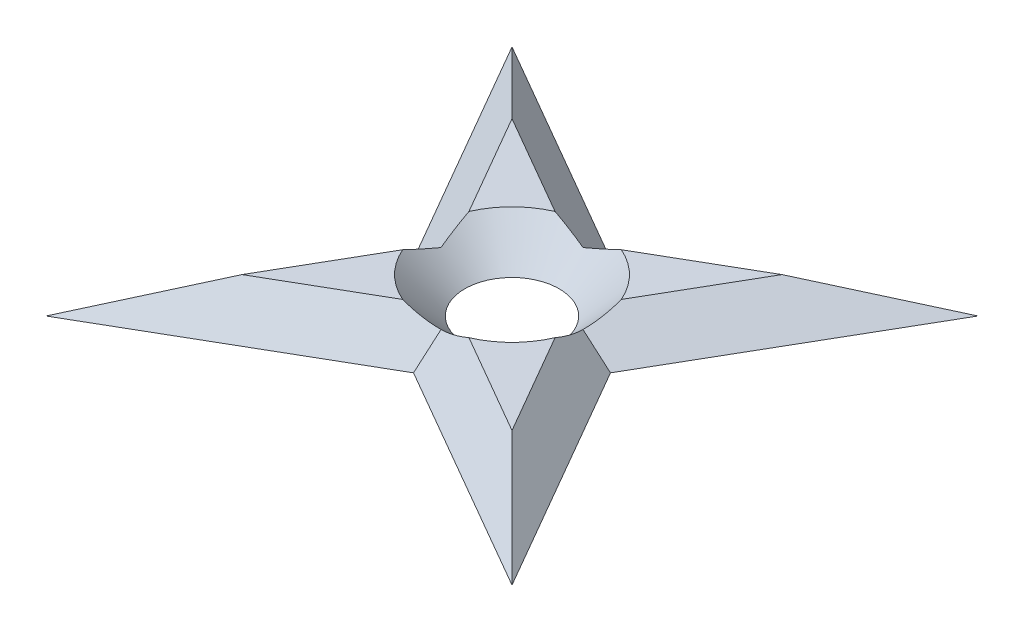
SolidWorks part; units mm, degrees
ref_plane "Front Plane" through (0, 0, 0) normal (0, 0, 1) x (1, 0, 0)
ref_plane "Top Plane" through (0, 0, 0) normal (0, 1, 0) x (1, 0, 0)
ref_plane "Right Plane" through (0, 0, 0) normal (1, 0, 0) x (0, 0, -1)
sketch "Sketch1" plane through (0, 0, 0) normal (0, 1, 0) x (1, 0, 0)
  line L0 (0, 0) -> (0, 234.4789) construction
  line L1 (0, 0) -> (250.2537, 0) construction
  line L2 (0, 0) -> (37.5, 64.9519)
  line L3 (0, 0) -> (64.9519, 37.5)
  line L5 (64.9519, 64.9519) -> (64.9519, 0) construction
  line L6 (129.9038, 0) -> (64.9519, 37.5)
  line L7 (129.9038, 0) -> (92.4038, 64.9519)
  line L8 (37.5, 64.9519) -> (92.4038, 64.9519) construction
  line L9 (129.9038, 129.9038) -> (92.4038, 64.9519)
  line L10 (129.9038, 129.9038) -> (64.9519, 92.4038)
  line L11 (0, 129.9038) -> (64.9519, 92.4038)
  line L12 (0, 129.9038) -> (37.5, 64.9519)
  circle A0 centre (64.9519, 64.9519) radius 13.155
  dimension "D5" = 26.31
  dimension "D1" = 75
  dimension "D2" = 30
  dimension "D3" = 30
  dimension "D4" = 75
extrude "Boss-Extrude1" add sketch "Sketch1" along normal blind 10
chamfer "Chamfer4" distance 10 angle 45 9 edges at (64.9519, 10, -51.7969) (18.75, 10, -32.476) (18.75, 10, -97.4279) (32.476, 10, -111.1538) (97.4279, 10, -111.1538) (111.1538, 10, -97.4279) (111.1538, 10, -32.476) (97.4279, 10, -18.75) (32.476, 10, -18.75)
